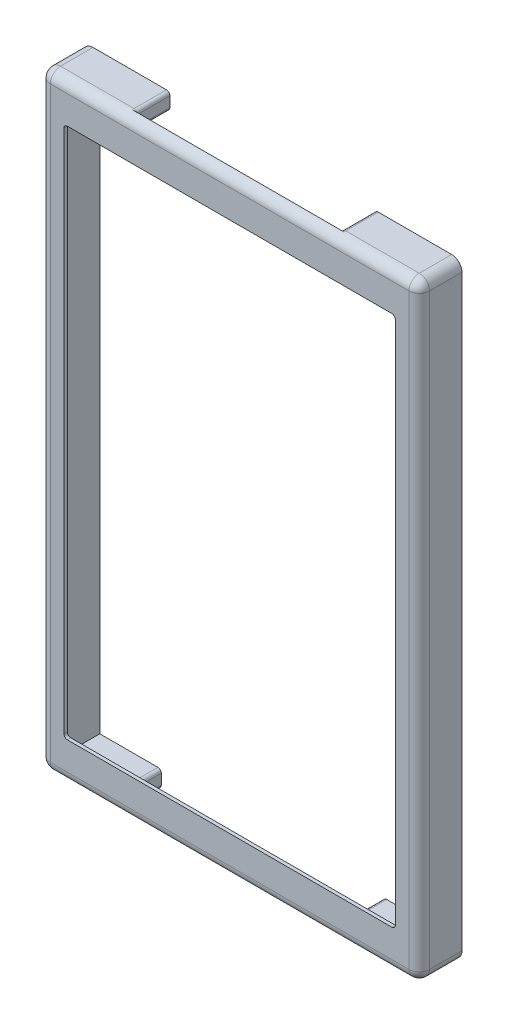
SolidWorks part; units mm, degrees
ref_plane "Front Plane" through (0, 0, 0) normal (0, 0, 1) x (1, 0, 0)
ref_plane "Top Plane" through (0, 0, 0) normal (0, 1, 0) x (1, 0, 0)
ref_plane "Right Plane" through (0, 0, 0) normal (1, 0, 0) x (0, 0, -1)
sketch "Sketch1" plane through (0, 0, 0) normal (0, 0, 1) x (1, 0, 0)
  line L0 (55.5, -89) -> (-55.5, -89)
  line L1 (50.5, 84) -> (-50.5, 84)
  line L2 (50.5, 84) -> (50.5, -84)
  line L3 (50.5, -84) -> (-50.5, -84)
  line L4 (-50.5, 84) -> (-50.5, -84)
  line L5 (50.5, 84) -> (-50.5, -84) construction
  line L6 (50.5, -84) -> (-50.5, 84) construction
  line L7 (-55.5, 89) -> (-55.5, -89)
  line L8 (55.5, 89) -> (-55.5, 89)
  line L9 (55.5, 89) -> (55.5, -89)
  point P0 (0, 0)
  dimension "D1" = 101
  dimension "D2" = 168
  dimension "D3" = 5
extrude "Boss-Extrude1" add sketch "Sketch1" along normal mid plane 12
sketch "Sketch2" plane through (0, 0, 6) normal (0, 0, 1) x (1, 0, 0)
  line L0 (-50.5, 84) -> (-50.5, -84) construction
  line L1 (55.5, -89) -> (-55.5, -89)
  line L2 (55.5, -89) -> (55.5, 89)
  line L3 (55.5, 89) -> (-55.5, 89)
  line L4 (-55.5, -89) -> (-55.5, 89)
  line L5 (55.5, -89) -> (-55.5, 89) construction
  line L6 (55.5, 89) -> (-55.5, -89) construction
  line L7 (48.5, 77.7748) -> (-48.5, 77.7748)
  line L8 (48.5, 77.7748) -> (48.5, -77.7748)
  line L9 (48.5, -77.7748) -> (-48.5, -77.7748)
  line L10 (-48.5, 77.7748) -> (-48.5, -77.7748)
  line L11 (48.5, 77.7748) -> (-48.5, -77.7748) construction
  line L12 (48.5, -77.7748) -> (-48.5, 77.7748) construction
  point P0 (0, 0)
  point P7 (0, 0)
  dimension "D1" = 2
extrude "Boss-Extrude2" add sketch "Sketch2" along normal mid plane 1
sketch "Sketch3" plane through (0, 84, 0) normal (0, -1, 0) x (1, 0, 0)
  line L0 (50.5, -6) -> (-50.5, -6) construction
  line L1 (-30, -6) -> (30, -6)
  line L2 (-30, -6) -> (-30, 4)
  line L3 (-30, 4) -> (30, 4)
  line L4 (30, -6) -> (30, 4)
  point P6 (0, -6)
  point P7 (0, -6)
  dimension "D1" = 60
  dimension "D2" = 10
extrude "Cut-Extrude1" cut sketch "Sketch3" against normal blind 77
sketch "Sketch4" plane through (0, -84, 0) normal (0, 1, 0) x (1, 0, 0)
  line L0 (-50.5, 6) -> (50.5, 6) construction
  line L1 (32.5, 11) -> (-32.5, 11)
  line L2 (32.5, 11) -> (32.5, 1)
  line L3 (32.5, 1) -> (-32.5, 1)
  line L4 (-32.5, 11) -> (-32.5, 1)
  line L5 (32.5, 11) -> (-32.5, 1) construction
  line L6 (32.5, 1) -> (-32.5, 11) construction
  point P0 (0, 6)
  dimension "D1" = 65
  dimension "D2" = 10
extrude "Cut-Extrude2" cut sketch "Sketch4" against normal blind 77
fillet "Fillet1" radius 1 4 edges at (-48.5, -77.7748, 6) (-48.5, 77.7748, 6) (48.5, 77.7748, 6) (48.5, -77.7748, 6)
fillet "Fillet2" radius 3 8 edges at (-55.5, 0, 6.5) (0, -89, 6.5) (55.5, 0, 6.5) (0, 89, 6.5) (55.5, 89, 0.25) (-55.5, 89, 0.25) (55.5, -89, 0.25) (-55.5, -89, 0.25)
fillet "Fillet3" radius 1 13 edges at (30, 88.9895, 3.7509) (-30, 88.9895, 3.7509) (30, 89, -1.25) (-30, 89, -1.25) (0, 84, 4) (32.5, -84, -3.5) (32.5, -89, -3.5) (-32.5, -89, -3.5) (0, -89, -1) (0, -84, -1) (-32.5, -84, -3.5) (30, 84, -1) (-30, 84, -1)
